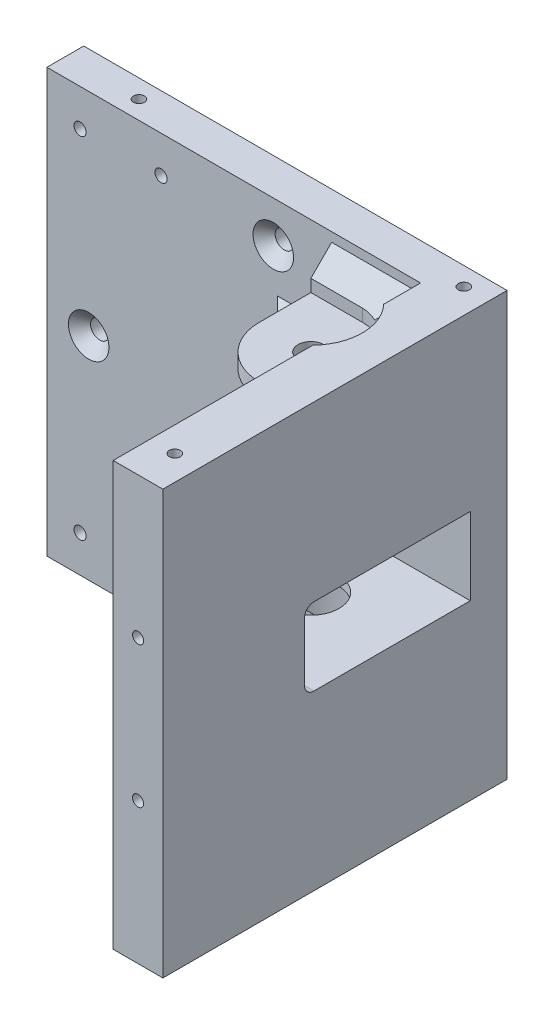
SolidWorks part; units mm, degrees
ref_plane "Top Plane" through (0, 0, 0) normal (0, 0, 1) x (1, 0, 0)
ref_plane "Right Plane" through (0, 0, 0) normal (0, 1, 0) x (1, 0, 0)
ref_plane "Front Plane" through (0, 0, 0) normal (1, 0, 0) x (0, 0, -1)
sketch "Sketch1" plane through (0, 0, 0) normal (0, 0, 1) x (1, 0, 0)
  line L0 (-75, 0) -> (40, 0) construction
  line L1 (-75, -57.5) -> (40, -57.5)
  line L2 (-75, -57.5) -> (-75, 57.5)
  line L3 (-75, 57.5) -> (40, 57.5)
  line L4 (40, -57.5) -> (40, 57.5)
  point P0 (0, 0)
  dimension "D1" = 115
  dimension "D2" = 40
  dimension "D3" = 115
extrude "Boss-Extrude1" add sketch "Sketch1" along normal blind 10
sketch "Sketch2" plane through (0, 0, 0) normal (0, 1, 0) x (1, 0, 0)
  line L0 (16.35, -29.65) -> (16.35, 0) construction
  line L1 (16.35, 0) -> (0, 0) construction
  line L2 (2.7, -29.65) -> (2.7, -10)
  line L3 (-75, -10) -> (40, -10) construction
  line L4 (2.7, -10) -> (30, -10)
  line L5 (30, -10) -> (30, -29.65)
  line L6 (-75, 0) -> (40, 0) construction
  line L7 (2.7, -29.65) -> (30, -29.65) construction
  circle A0 centre (16.35, -29.65) radius 9.65
  arc A1 (2.7, -29.65) -> (30, -29.65) centre (16.35, -29.65) ccw
  dimension "D1" = 19.3
  dimension "D3" = 10
  dimension "D4" = 4
  dimension "D2" = 10
extrude "Boss-Extrude2" add sketch "Sketch2" along normal mid plane 40
sketch "Sketch3" plane through (0, 0, 0) normal (0, 1, 0) x (1, 0, 0)
  line L3 (2.7, -10) -> (2.7, -29.65)
  line L4 (30, -10) -> (2.7, -10)
  line L5 (30, -29.65) -> (30, -10)
  line L6 (2.7, -10) -> (2.7, -29.65)
  line L7 (30, -10) -> (2.7, -10)
  line L8 (30, -29.65) -> (30, -10)
  arc A1 (2.7, -29.65) -> (30, -29.65) centre (16.35, -29.65) ccw
  arc A2 (2.7, -29.65) -> (30, -29.65) centre (16.35, -29.65) ccw
  dimension "D1" = 0
extrude "Cut-Extrude1" cut sketch "Sketch3" against normal mid plane 21
chamfer "Chamfer1" distance 15 angle 45 6 edges at (2.7, -15.25, 10) (30, -15.25, 10) (16.35, -20, 10) (2.7, 15.25, 10) (30, 15.25, 10) (16.35, 20, 10)
sketch "Sketch4" plane through (40, 0, 0) normal (1, 0, 0) x (0, 0, -1)
  line L0 (0, -57.5) -> (0, 57.5) construction
  line L1 (-10, -10.5) -> (-52.5, -10.5)
  line L2 (-10, -10.5) -> (-10, -57.5)
  line L3 (-10, -57.5) -> (-93.5, -57.5)
  line L4 (-93.5, 0) -> (-93.5, -57.5)
  line L7 (-93.5, 0) -> (-55, 0)
  line L10 (-93.5, -30.75) -> (-93.5, 30.75) construction
  line L11 (0, 0) -> (-55, 0) construction
  line L12 (-55, -8) -> (-55, 0)
  line L13 (-10, -10.5) -> (-10, 10.5) construction
  line L14 (-10, -57.5) -> (-10, -35) construction
  arc A1 (-52.5, -10.5) -> (-55, -8) centre (-52.5, -8) cw
  dimension "D1" = 45
  dimension "D2" = 8
extrude "Boss-Extrude3" add sketch "Sketch4" against normal blind 13.5
mirror "Mirror3" about plane through (26.5, 0, 93.5) normal (0, 1, 0) of "Boss-Extrude3"
chamfer "Chamfer2" distance 21 angle 45 1 edges at (26.5, -15.25, 38.7769) first distance on face at (26.5, 0, 40.5089)
sketch "Sketch5" plane through (0, 0, 93.5) normal (0, 0, 1) x (1, 0, 0)
  line L0 (33.25, 57.5) -> (33.25, 19.1667) construction
  line L1 (26.5, 57.5) -> (40, 57.5) construction
  line L2 (33.25, 19.1667) -> (33.25, -19.1667) construction
  line L3 (33.25, -19.1667) -> (33.25, -57.5) construction
  line L4 (26.5, -57.5) -> (40, -57.5) construction
  circle A0 centre (33.25, 19.1667) radius 1.5
  circle A1 centre (33.25, -19.1667) radius 1.5
  dimension "D1" = 3
extrude "Cut-Extrude2" cut sketch "Sketch5" against normal blind 10
sketch "Sketch6" plane through (0, 0, 10) normal (0, 0, 1) x (1, 0, 0)
  line L0 (-66, -47.5) -> (-44, -47.5) construction
  line L1 (-44, -47.5) -> (-44, 47.5) construction
  line L2 (-44, 47.5) -> (-66, 47.5) construction
  line L3 (0, 0) -> (-44, 0) construction
  line L4 (26.5, 57.5) -> (-75, 57.5) construction
  line L5 (-75, 57.5) -> (-75, -57.5) construction
  line L6 (-35, 47.5) -> (-44, 47.5) construction
  line L7 (-35, 57.5) -> (-35, 23.75) construction
  line L10 (-66, 47.5) -> (-75, 47.5) construction
  circle A0 centre (-44, 47.5) radius 1.65
  circle A1 centre (-66, 47.5) radius 1.65
  circle A2 centre (-44, -47.5) radius 1.65
  circle A3 centre (-66, -47.5) radius 1.65
  dimension "D1" = 10
  dimension "D3" = 3.3
  dimension "D2" = 9
extrude "Cut-Extrude3" cut sketch "Sketch6" against normal through all
sketch "Sketch7" plane through (0, 0, 10) normal (0, 0, 1) x (1, 0, 0)
  line L0 (-13.5, -46.25) -> (-13.5, -57.5) construction
  line L1 (-13.5, 46.25) -> (-13.5, 35) construction
  line L2 (0, 0) -> (11.6749, 0) construction
  line L3 (-12.3, 35) -> (26.5, 35) construction
  line L4 (-75, -57.5) -> (26.5, -57.5) construction
  line L6 (26.5, 57.5) -> (-75, 57.5) construction
  line L7 (-13.5, 57.5) -> (-13.5, 46.25) construction
  circle A0 centre (-63.65, 0) radius 2.5
  circle A1 centre (-13.5, -46.25) radius 2.5
  circle A2 centre (-13.5, 46.25) radius 2.5
  dimension "D1" = 5
  dimension "D2" = 40
extrude "Cut-Extrude4" cut sketch "Sketch7" against normal through all
sketch "Sketch8" plane through (0, 20, 0) normal (0, 1, 0) x (1, 0, 0)
  circle A0 centre (16.35, -29.65) radius 9.65
  circle A1 centre (16.35, -29.65) radius 7.65
  arc A2 (7.8942, -25) -> (24.8058, -25) centre (16.35, -29.65) ccw construction
  dimension "D1" = 2
extrude "Boss-Extrude4" add sketch "Sketch8" against normal blind 2.5 from offset 7 offset against normal yes
sketch "Sketch11" plane through (0, 57.5, 0) normal (0, 1, 0) x (1, 0, 0)
  line L0 (33.25, -83.5) -> (33.25, -5) construction
  line L1 (33.25, -5) -> (-55, -5) construction
  line L2 (-75, -5) -> (-55, -5) construction
  line L3 (-75, -10) -> (-75, 0) construction
  line L5 (26.5, -93.5) -> (40, -93.5) construction
  line L6 (33.25, -93.5) -> (33.25, -83.5) construction
  circle A0 centre (33.25, -83.5) radius 1.5
  circle A1 centre (33.25, -5) radius 1.5
  circle A2 centre (-55, -5) radius 1.5
  dimension "D1" = 3
  dimension "D2" = 10
  dimension "D3" = 20
extrude "Cut-Extrude6" cut sketch "Sketch11" against normal blind 10
mirror "Mirror4" about plane through (0, 0, 0) normal (0, 1, 0) of "Cut-Extrude6", "Boss-Extrude4"
ref_plane "Plane1" through (0, 42, 0) normal (0, 1, 0) x (1, 0, 0)
sketch "Sketch9" plane through (0, 42, 0) normal (0, 1, 0) x (1, 0, 0)
  line L1 (26.5, -10) -> (2.35, -10)
  line L2 (26.5, -10) -> (26.5, -43.65)
  line L3 (26.5, -43.65) -> (2.35, -43.65)
  line L4 (2.35, -10) -> (2.35, -43.65)
  circle A0 centre (16.35, -29.65) radius 3.5
  circle A2 centre (16.35, -29.65) radius 14 construction
  dimension "D1" = 7
  dimension "D2" = 28
extrude "Boss-Extrude5" add sketch "Sketch9" along normal blind 4
chamfer "Chamfer3" distance 9 angle 45 3 edges at (26.5, 44, 43.65) (26.5, 46, 26.825) (14.425, 46, 10)
chamfer "Chamfer4" distance 5 angle 45 3 edges at (26.5, 42, 31.325) (26.5, 38.5, 10) (14.425, 42, 10)
sketch "Sketch10" plane through (0, 46, 0) normal (0, 1, 0) x (1, 0, 0)
  line L0 (2.35, -19) -> (2.35, -43.65) construction
  line L1 (16.35, -43.65) -> (2.35, -43.65)
  line L3 (16.35, -15.65) -> (2.35, -15.65)
  line L4 (2.35, -43.65) -> (2.35, -15.65)
  arc A0 (16.35, -43.65) -> (16.35, -15.65) centre (16.35, -29.65) ccw
  dimension "D1" = 28
extrude "Cut-Extrude5" cut sketch "Sketch10" along normal through all
fillet "Fillet1" radius 14 1 edges at (2.35, 44, 43.65)
chamfer "Chamfer5" distance 3 angle 45 3 edges at (-11, -46.25, 10) (-61.15, 0, 10) (-11, 46.25, 10)
sketch "Sketch12" plane through (0, 42, 0) normal (0, -1, 0) x (1, 0, 0)
  circle A0 centre (16.35, 29.65) radius 6
  dimension "D1" = 12
extrude "Cut-Extrude7" cut sketch "Sketch12" along normal blind 7
sketch "Sketch13" plane through (0, 0, 0) normal (0, 0, -1) x (-1, 0, 0)
  line L0 (66, 50.9641) -> (69, 49.2321)
  line L1 (69, 49.2321) -> (69, 45.7679)
  line L2 (69, 45.7679) -> (66, 44.0359)
  line L3 (66, 44.0359) -> (63, 45.7679)
  line L4 (63, 45.7679) -> (63, 49.2321)
  line L5 (63, 49.2321) -> (66, 50.9641)
  line L6 (66, 47.5) -> (44, 47.5) construction
  line L7 (44, 47.5) -> (44, -47.5) construction
  line L8 (44, -47.5) -> (66, -47.5) construction
  line L9 (47, 45.7679) -> (47, 49.2321)
  line L10 (44, 0) -> (63.65, 0) construction
  line L11 (44, 44.0359) -> (47, 45.7679)
  line L12 (55, -47.5) -> (55, 47.5) construction
  line L13 (41, 45.7679) -> (44, 44.0359)
  line L14 (41, 49.2321) -> (41, 45.7679)
  line L15 (44, 50.9641) -> (41, 49.2321)
  line L16 (47, 49.2321) -> (44, 50.9641)
  line L17 (63, -45.7679) -> (63, -49.2321)
  line L18 (66, -44.0359) -> (63, -45.7679)
  line L19 (69, -45.7679) -> (66, -44.0359)
  line L20 (69, -49.2321) -> (69, -45.7679)
  line L21 (66, -50.9641) -> (69, -49.2321)
  line L22 (63, -49.2321) -> (66, -50.9641)
  line L23 (44, -44.0359) -> (47, -45.7679)
  line L24 (41, -45.7679) -> (44, -44.0359)
  line L25 (41, -49.2321) -> (41, -45.7679)
  line L26 (44, -50.9641) -> (41, -49.2321)
  line L27 (47, -49.2321) -> (44, -50.9641)
  line L28 (47, -45.7679) -> (47, -49.2321)
  circle A0 centre (66, 47.5) radius 3.4641 construction
  dimension "D1" = 6
extrude "Cut-Extrude8" cut sketch "Sketch13" against normal blind 4
chamfer "Chamfer6" distance 16 angle 45 1 edges at (26.5, -46.25, 10)
